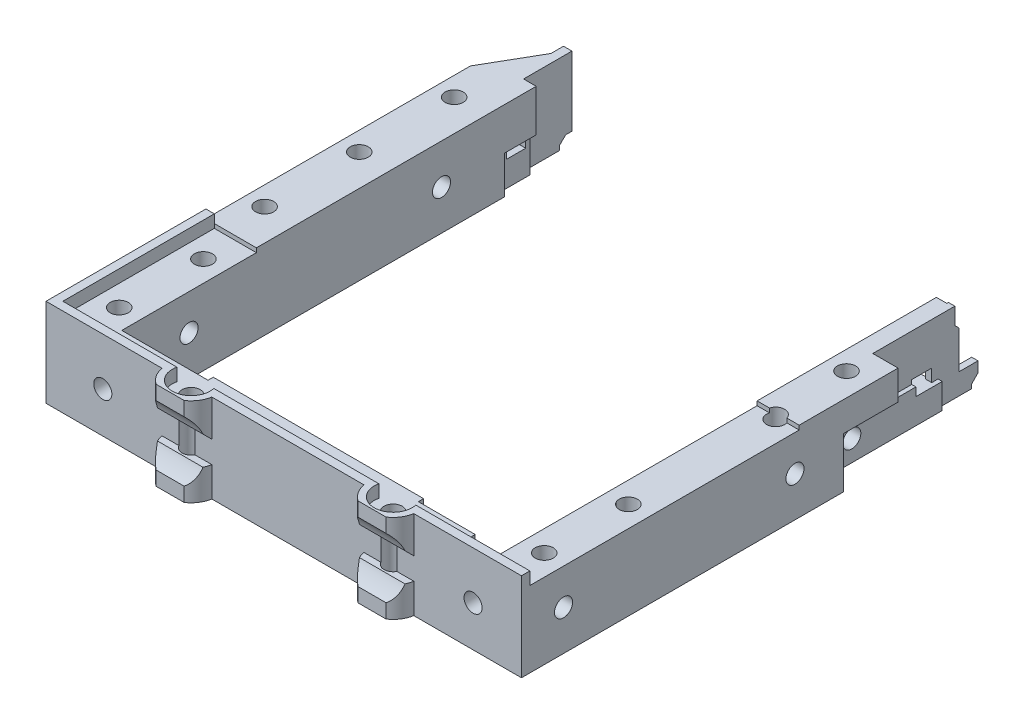
SolidWorks part; units mm, degrees
ref_plane "前视基准面" through (0, 0, 0) normal (0, 0, 1) x (1, 0, 0)
ref_plane "上视基准面" through (0, 0, 0) normal (0, 1, 0) x (1, 0, 0)
ref_plane "右视基准面" through (0, 0, 0) normal (1, 0, 0) x (0, 0, -1)
sketch "草图2" plane through (0, 0, 0) normal (0, 1, 0) x (1, 0, 0)
  line L0 (0, 0) -> (0, -10) construction
  line L1 (-45.5, 0) -> (45.5, 0)
  line L2 (45.5, 0) -> (45.5, 93)
  line L3 (45.5, 93) -> (55.5, 93)
  line L4 (55.5, 93) -> (55.5, -10)
  line L5 (55.5, -10) -> (-55.5, -10)
  line L6 (-45.5, 93) -> (-55.5, 93)
  line L7 (-55.5, 93) -> (-55.5, -10)
  line L8 (-45.5, 0) -> (-45.5, 93)
  dimension "D1" = 10
  dimension "D2" = 10
  dimension "D3" = 45.5
  dimension "D4" = 93
extrude "凸台-拉伸1" add sketch "草图2" along normal blind 18
sketch "草图3" plane through (0, 18, 0) normal (0, 1, 0) x (1, 0, 0)
  line L0 (55.5, 93) -> (45.5, 93) construction
  line L1 (45.5, 93) -> (45.5, 0) construction
  circle A0 centre (50, 76.75) radius 2.15
  dimension "D1" = 16.25
  dimension "D2" = 4.3
  dimension "D3" = 4.5
extrude "切除-拉伸1" cut sketch "草图3" against normal through all
sketch "草图4" plane through (55.5, 0, 0) normal (1, 0, 0) x (0, 0, -1)
  line L0 (-10, 0) -> (93, 0) construction
  line L1 (93, 18) -> (85.5, 18)
  line L2 (93, 18) -> (93, 0)
  line L3 (93, 0) -> (85.5, 0)
  line L4 (85.5, 18) -> (85.5, 0)
  line L5 (93, 18) -> (85.5, 0) construction
  line L6 (93, 0) -> (85.5, 18) construction
  point P4 (89.25, 9)
  dimension "D1" = 7.5
extrude "切除-拉伸2" cut sketch "草图4" against normal blind 6
sketch "草图5" plane through (55.5, 0, 0) normal (1, 0, 0) x (0, 0, -1)
  line L0 (85.5, 18) -> (85.5, 0) construction
  line L1 (85.5, 12) -> (70.5, 12)
  line L2 (85.5, 12) -> (85.5, 0)
  line L3 (85.5, 0) -> (70.5, 0)
  line L4 (70.5, 12) -> (70.5, 0)
  line L5 (85.5, 12) -> (70.5, 0) construction
  line L6 (85.5, 0) -> (70.5, 12) construction
  line L7 (-10, 0) -> (85.5, 0) construction
  line L8 (-10, 18) -> (85.5, 18) construction
  point P4 (78, 6)
  dimension "D1" = 6
  dimension "D2" = 15
extrude "切除-拉伸3" cut sketch "草图5" against normal up to surface (6 mm away) up to face at (49.5, 9, -89.25)
sketch "草图6" plane through (49.5, 0, 0) normal (1, 0, 0) x (0, 0, -1)
  line L1 (93, 0) -> (91, 0)
  line L2 (93, 0) -> (93, 9)
  line L3 (93, 9) -> (91, 9)
  line L4 (91, 0) -> (91, 9)
  line L5 (93, 0) -> (91, 9) construction
  line L6 (93, 9) -> (91, 0) construction
  point P4 (92, 4.5)
  dimension "D1" = 9
  dimension "D2" = 2
extrude "切除-拉伸4" cut sketch "草图6" against normal up to next
sketch "草图7" plane through (0, 18, 0) normal (0, 1, 0) x (1, 0, 0)
  line L0 (-45.5, 0) -> (-45.5, 93) construction
  line L1 (-55.5, 93) -> (-45.5, 93)
  line L2 (-55.5, 93) -> (-55.5, 32)
  line L3 (-55.5, 32) -> (-45.5, 32)
  line L4 (-45.5, 93) -> (-45.5, 32)
  line L5 (-55.5, 93) -> (-45.5, 32) construction
  line L6 (-55.5, 32) -> (-45.5, 93) construction
  point P4 (-50.5, 62.5)
  dimension "D1" = 61
extrude "凸台-拉伸2" add sketch "草图7" along normal blind 1
sketch "草图8" plane through (-55.5, 0, 0) normal (-1, 0, 0) x (0, 0, 1)
  line L1 (-32, 19) -> (-93, 19)
  line L2 (-32, 19) -> (-32, 0)
  line L3 (-32, 0) -> (-93, 0)
  line L4 (-93, 19) -> (-93, 0)
  line L5 (-32, 19) -> (-93, 0) construction
  line L6 (-32, 0) -> (-93, 19) construction
  point P4 (-62.5, 9.5)
extrude "凸台-拉伸3" add sketch "草图8" along normal blind 4
sketch "草图9" plane through (-55.5, 0, 0) normal (-1, 0, 0) x (0, 0, 1)
  line L1 (10, 0) -> (-32, 0)
  line L2 (10, 0) -> (10, 19)
  line L3 (10, 19) -> (-32, 19)
  line L4 (-32, 0) -> (-32, 19)
  line L5 (10, 0) -> (-32, 19) construction
  line L6 (10, 19) -> (-32, 0) construction
  point P4 (-11, 9.5)
extrude "凸台-拉伸4" add sketch "草图9" along normal blind 2
sketch "草图10" plane through (0, 18, 0) normal (0, 1, 0) x (1, 0, 0)
  line L0 (-57.5, -10) -> (-57.5, 32) construction
  line L1 (-55.5, -10) -> (55.5, -10) construction
  circle A0 centre (-50.5, 4.4) radius 2.15
  circle A1 centre (-50.5, 24.4) radius 2.15
  circle A2 centre (-24, -5) radius 2.15
  circle A3 centre (24, -5) radius 2.15
  dimension "D1" = 4.3
  dimension "D2" = 7
  dimension "D3" = 14.4
  dimension "D4" = 20
  dimension "D5" = 5
  dimension "D6" = 33.5
  dimension "D7" = 48
extrude "切除-拉伸5" cut sketch "草图10" against normal blind 6
sketch "草图11" plane through (0, 0, 0) normal (0, 0, -1) x (-1, 0, 0)
  line L0 (-45.5, 18) -> (45.5, 18) construction
  line L1 (-25, 18) -> (25, 18)
  line L2 (-25, 18) -> (-25, 0)
  line L3 (-25, 0) -> (25, 0)
  line L4 (25, 18) -> (25, 0)
  line L5 (-25, 18) -> (25, 0) construction
  line L6 (-25, 0) -> (25, 18) construction
  line L7 (-45.5, 0) -> (45.5, 0) construction
  point P4 (0, 9)
  dimension "D1" = 50
extrude "凸台-拉伸5" add sketch "草图11" along normal blind 1.25
sketch "草图12" plane through (0, 18, 0) normal (0, 1, 0) x (1, 0, 0)
  line L0 (49.5, 93) -> (45.5, 93)
  line L1 (45.5, 93) -> (45.5, 60)
  line L2 (45.5, 93) -> (45.5, 0) construction
  line L3 (45.5, 60) -> (55.5, 60)
  line L4 (55.5, -10) -> (55.5, 85.5) construction
  line L5 (55.5, 60) -> (55.5, 85.5)
  line L6 (55.5, 85.5) -> (49.5, 85.5)
  line L7 (49.5, 85.5) -> (49.5, 93)
  circle A0 centre (50, 76.75) radius 2.15 construction
  circle A1 centre (50, 76.75) radius 2.15
  dimension "D1" = 33
extrude "凸台-拉伸6" add sketch "草图12" along normal blind 1
sketch "草图13" plane through (0, 18, 0) normal (0, 1, 0) x (1, 0, 0)
  line L1 (45.5, 0) -> (38.5, 0)
  line L2 (45.5, 0) -> (45.5, -2)
  line L3 (45.5, -2) -> (38.5, -2)
  line L4 (38.5, 0) -> (38.5, -2)
  line L5 (45.5, 0) -> (38.5, -2) construction
  line L6 (45.5, -2) -> (38.5, 0) construction
  point P4 (42, -1)
  dimension "D1" = 7
  dimension "D2" = 2
extrude "切除-拉伸6" cut sketch "草图13" against normal up to surface (18 mm away) up to face at (4.075, 0, -39.3889)
sketch "草图14" plane through (0, 18, 0) normal (0, 1, 0) x (1, 0, 0)
  line L0 (55.5, -10) -> (55.5, 60) construction
  line L1 (-57.5, -10) -> (-27.3166, -10)
  line L2 (-57.5, -10) -> (-57.5, -6)
  line L3 (-57.5, -6) -> (-29.9161, -6)
  line L4 (55.5, -10) -> (55.5, -6)
  line L5 (-18.0839, -6) -> (18.0839, -6)
  line L6 (-20.6834, -10) -> (20.6834, -10)
  line L7 (29.9161, -6) -> (55.5, -6)
  line L8 (27.3166, -10) -> (55.5, -10)
  arc A0 (-29.9161, -6) -> (-27.3166, -10) centre (-24, -5) ccw
  arc A1 (18.0839, -6) -> (20.6834, -10) centre (24, -5) ccw
  arc A2 (-20.6834, -10) -> (-18.0839, -6) centre (-24, -5) ccw
  arc A3 (27.3166, -10) -> (29.9161, -6) centre (24, -5) ccw
  dimension "D2" = 12
  dimension "D3" = 12
  dimension "D1" = 4
extrude "切除-拉伸7" cut sketch "草图14" against normal through all and the other way through all
sketch "草图16" plane through (0, 18, 0) normal (0, 1, 0) x (1, 0, 0)
  line L0 (55.5, -6) -> (55.5, 60) construction
  line L1 (-55.5, -6) -> (-29.9161, -6)
  line L2 (-55.5, -6) -> (-55.5, -4)
  line L3 (-55.5, -4) -> (-29.9161, -4)
  line L4 (55.5, -6) -> (55.5, -4)
  line L5 (-18.0839, -4) -> (18.0839, -4)
  line L6 (-18.0839, -6) -> (18.0839, -6)
  line L7 (29.9161, -4) -> (55.5, -4)
  line L8 (29.9161, -6) -> (55.5, -6)
  arc A0 (-29.9161, -4) -> (-29.9161, -6) centre (-24, -5) ccw
  arc A1 (18.0839, -4) -> (18.0839, -6) centre (24, -5) ccw
  arc A2 (-18.0839, -6) -> (-18.0839, -4) centre (-24, -5) ccw
  arc A3 (29.9161, -6) -> (29.9161, -4) centre (24, -5) ccw
  dimension "D1" = 2
extrude "凸台-拉伸7" add sketch "草图16" along normal up to surface (1 mm away) up to face at (-54.5, 19, -37.75)
sketch "草图18" plane through (0, 19, 0) normal (0, 1, 0) x (1, 0, 0)
  line L0 (-53, 86.45) -> (-53, 41.45) construction
  line L1 (-59.5, 32) -> (-59.5, 93) construction
  line L2 (-45.5, 93) -> (-59.5, 93) construction
  circle A0 centre (-53, 86.45) radius 2.15
  circle A1 centre (-53, 63.95) radius 2.15
  circle A2 centre (-53, 41.45) radius 2.15
  dimension "D1" = 4.3
  dimension "D2" = 6.5
  dimension "D3" = 6.55
  dimension "D4" = 45
extrude "切除-拉伸8" cut sketch "草图18" against normal blind 6
sketch "草图19" plane through (0, 12, 0) normal (0, 1, 0) x (1, 0, 0)
  circle A0 centre (24, -5) radius 2.15 construction
  circle A1 centre (-24, -5) radius 2.15 construction
  circle A2 centre (24, -5) radius 2.15
  circle A3 centre (-24, -5) radius 2.15
extrude "切除-拉伸9" cut sketch "草图19" against normal through all
sketch "草图20" plane through (0, 13, 0) normal (0, 1, 0) x (1, 0, 0)
  line L0 (0, 0) -> (0, 86.45) construction
  circle A0 centre (-50.5, 4.4) radius 2.15 construction
  circle A1 centre (-50.5, 24.4) radius 2.15 construction
  circle A2 centre (-53, 41.45) radius 2.15 construction
  circle A3 centre (-53, 63.95) radius 2.15 construction
  circle A4 centre (-53, 86.45) radius 2.15 construction
  circle A5 centre (-50.5, 4.4) radius 2.15
  circle A6 centre (-50.5, 24.4) radius 2.15
  circle A7 centre (-53, 41.45) radius 2.15
  circle A8 centre (-53, 63.95) radius 2.15
  circle A9 centre (-53, 86.45) radius 2.15
  circle A10 centre (50.5, 24.4) radius 2.15
  circle A11 centre (50.5, 4.4) radius 2.15
extrude "切除-拉伸10" cut sketch "草图20" against normal through all and the other way through all
sketch "草图21" plane through (0, 0, 0) normal (0, -1, 0) x (1, 0, 0)
  line L1 (-45.5, -93) -> (45.5, -93)
  line L2 (-45.5, -93) -> (-45.5, 2)
  line L3 (-45.5, 2) -> (45.5, 2)
  line L4 (45.5, -93) -> (45.5, 2)
extrude "凸台-拉伸8" [suppressed] add sketch "草图21" against normal blind 2
sketch "草图22" [suppressed] plane through (0, 2, 0) normal (0, 1, 0) x (1, 0, 0)
  line L1 (38.5, 0) -> (45.5, 0)
  line L2 (38.5, 0) -> (38.5, -2)
  line L3 (38.5, -2) -> (45.5, -2)
  line L4 (45.5, 0) -> (45.5, -2)
extrude "凸台-拉伸9" [suppressed] add sketch "草图22" along normal blind 15
sketch "草图23" plane through (0, 0, -32) normal (0, 0, 1) x (1, 0, 0)
  line L4 (-59.5, 0) -> (-57.5, 0)
  line L5 (-57.5, 0) -> (-57.5, 19)
  line L6 (-57.5, 19) -> (-59.5, 19)
  line L7 (-59.5, 19) -> (-59.5, 0)
  line L8 (-59.5, 0) -> (-57.5, 0)
  line L9 (-57.5, 0) -> (-57.5, 19)
  line L10 (-57.5, 19) -> (-59.5, 19)
  line L11 (-59.5, 19) -> (-59.5, 0)
  dimension "D1" = 0
extrude "切除-拉伸11" cut sketch "草图23" against normal through all
sketch "草图24" plane through (0, 19, 0) normal (0, 1, 0) x (1, 0, 0)
  line L0 (-45.5, 93) -> (-49.5, 93)
  line L1 (-45.5, 93) -> (-57.5, 93) construction
  line L2 (-49.5, 93) -> (-45.5, 89)
  line L3 (-45.5, 32) -> (-45.5, 93) construction
  line L4 (-45.5, 89) -> (-45.5, 93)
  dimension "D1" = 4
  dimension "D2" = 4
sketch "草图26" plane through (49.5, 0, 0) normal (1, 0, 0) x (0, 0, -1)
  line L0 (91, 0) -> (91, 6)
  line L2 (91, 9) -> (91, 0) construction
  line L3 (91, 6) -> (98, 6)
  line L4 (98, 6) -> (98, 9)
  line L5 (98, 9) -> (93, 9)
  line L6 (93, 9) -> (93, 19)
  line L7 (93, 19) -> (107, 19)
  line L8 (107, 19) -> (107, 0)
  line L9 (107, 0) -> (91, 0)
  dimension "D1" = 6
  dimension "D2" = 5
  dimension "D3" = 16
extrude "凸台-拉伸10" add sketch "草图26" against normal offset from surface (3 mm away) 1 contours L8 L9 L0 L3 L4 L5 L6 L7 up to face at (45.5, 11.5, -60.5)
sketch "草图27" plane through (46.5, 0, 0) normal (-1, 0, 0) x (0, 0, 1)
  line L0 (-98, 13) -> (-98, 0)
  line L1 (-91, 0) -> (-107, 0) construction
  line L2 (-98, 0) -> (-107, 0)
  line L3 (-107, 0) -> (-107, 19)
  line L4 (-98, 9) -> (-98, 6) construction
  line L5 (-93, 9) -> (-98, 9) construction
  line L6 (-98, 13) -> (-101.4641, 19)
  line L7 (-107, 19) -> (-93, 19) construction
  line L8 (-107, 19) -> (-101.4641, 19)
  dimension "D1" = 4
  dimension "D2" = 150
extrude "切除-拉伸13" cut sketch "草图27" against normal offset from surface (1.5 mm away) 2.5 up to face at (45.5, 11.5, -60.5)
sketch "草图28" plane through (46.5, 0, 0) normal (-1, 0, 0) x (0, 0, 1)
  line L5 (-101.4641, 19) -> (-98, 13)
  line L6 (-98, 13) -> (-98, 9)
  line L7 (-98, 9) -> (-93, 9)
  line L8 (-93, 9) -> (-93, 19)
  line L9 (-93, 19) -> (-101.4641, 19)
  line L10 (-101.4641, 19) -> (-98, 13)
  line L11 (-98, 13) -> (-98, 9)
  line L12 (-98, 9) -> (-93, 9)
  line L13 (-93, 9) -> (-93, 19)
  line L14 (-93, 19) -> (-101.4641, 19)
  dimension "D1" = 0
extrude "凸台-拉伸11" add sketch "草图28" along normal up to surface (1 mm away) up to face at (45.5, 11.5, -60.5)
sketch "草图29" plane through (49.5, 0, 0) normal (1, 0, 0) x (0, 0, -1)
  line L0 (85.5, 12) -> (85.5, 6)
  line L1 (85.5, 6) -> (99, 6)
  line L3 (99, 6) -> (99, 0)
  line L4 (99, 0) -> (78.8411, 0)
  line L5 (70.5, 0) -> (70.5, 12)
  line L6 (70.5, 12) -> (74.6589, 12)
  line L7 (98, 6) -> (98, 9) construction
  line L8 (91, 6) -> (98, 6) construction
  line L9 (78.8411, 12) -> (78.8411, 0)
  line L10 (78.8411, 0) -> (78.8411, 12) construction
  line L11 (74.6589, 0) -> (74.6589, 12)
  line L12 (78.8411, 12) -> (85.5, 12)
  line L13 (74.6589, 0) -> (70.5, 0)
  dimension "D1" = 1
extrude "凸台-拉伸12" add sketch "草图29" along normal offset from surface (1 mm away) 5 up to face at (45.5, 11.6667, -66.1627)
fillet "圆角1" radius 1 1 edges at (50, 6, -85.5)
sketch "草图30" plane through (49.5, 0, 0) normal (1, 0, 0) x (0, 0, -1)
  line L2 (107, 19) -> (107, 0) construction
  line L3 (107, 11) -> (107, 19)
  line L4 (107, 19) -> (101.5, 19)
  line L6 (107, 11) -> (102.5, 11)
  line L7 (101.5, 12) -> (101.5, 19)
  line L8 (85.5, 19) -> (85.5, 12) construction
  arc A0 (102.5, 11) -> (101.5, 12) centre (102.5, 12) cw
  dimension "D2" = 1
  dimension "D1" = 8
  dimension "D3" = 16
extrude "切除-拉伸14" cut sketch "草图30" against normal up to next
sketch "草图31" plane through (49.5, 0, 0) normal (1, 0, 0) x (0, 0, -1)
  line L0 (107, 1) -> (108.5, 2.5)
  line L1 (107, 11) -> (107, 0) construction
  line L2 (108.5, 2.5) -> (108.5, 11)
  line L3 (108.5, 11) -> (107, 11)
  line L6 (99, 0) -> (107, 0) construction
  line L8 (107, 11) -> (107, 1)
  dimension "D1" = 1.5
  dimension "D2" = 1
  dimension "D3" = 45
extrude "凸台-拉伸13" add sketch "草图31" against normal up to surface (1.5 mm away) up to face at (48, 9.9793, -101.2757)
sketch "草图32" plane through (49.5, 0, 0) normal (1, 0, 0) x (0, 0, -1)
  line L0 (99, 6) -> (86.5, 6) construction
  line L1 (91, 9) -> (92.75, 9)
  line L2 (91, 9) -> (91, 6)
  line L3 (91, 6) -> (92.75, 6)
  line L4 (92.75, 9) -> (92.75, 6)
  dimension "D1" = 1.75
extrude "凸台-拉伸14" add sketch "草图32" against normal up to surface (4 mm away) up to face at (45.5, 11.6667, -66.1627)
chamfer "倒角1" distance 1 angle 60 1 edges at (45.5, 6, -91.875) first distance on face at (46, 6, -91.875)
sketch "草图33" plane through (0, 19, 0) normal (0, 1, 0) x (1, 0, 0)
  circle A0 centre (-53, 86.45) radius 2.15
  circle A1 centre (-53, 86.45) radius 2.15 construction
extrude "凸台-拉伸16" add sketch "草图33" against normal up to surface (19 mm away) up to face at (19.4221, 0, -39.5712)
sketch "草图34" plane through (0, 19, 0) normal (0, 1, 0) x (1, 0, 0)
  line L1 (-45.5, 93) -> (-57.5, 93) construction
  line L2 (-53, 86.5) -> (-53, 63.95) construction
  circle A0 centre (-53, 86.5) radius 2.15
  circle A1 centre (-53, 63.95) radius 2.15 construction
  dimension "D2" = 6.5
extrude "切除-拉伸15" cut sketch "草图34" against normal up to next
sketch "草图35" plane through (0, 19, 0) normal (0, 1, 0) x (1, 0, 0)
  circle A0 centre (-53, 86.5) radius 5
  circle A1 centre (-53, 86.5) radius 2.15
  circle A2 centre (-53, 86.5) radius 2.15 construction
  dimension "D1" = 10
sketch "草图36" plane through (-57.5, 0, 0) normal (-1, 0, 0) x (0, 0, 1)
  line L0 (-93, 6) -> (-98.5, 6)
  line L1 (-93, 0) -> (-93, 19) construction
  line L2 (-98.5, 6) -> (-98.5, 9)
  line L3 (-98.5, 9) -> (-93, 9)
  line L4 (-91, 0) -> (-98, 0) construction
  line L5 (-92.75, 9) -> (-98, 9) construction
  line L6 (-93, 6) -> (-93, 0)
  line L7 (-93, 0) -> (-107, 0)
  line L8 (-107, 0) -> (-98, 0) construction
  line L9 (-93, 0) -> (6, 0) construction
  line L10 (-107, 0) -> (-107, 1)
  line L11 (-107, 1) -> (-108.5, 2.5)
  line L12 (-108.5, 2.5) -> (-110, 2.5)
  line L13 (-110, 2.5) -> (-110, 19)
  line L14 (-110, 19) -> (-93, 19)
  line L15 (-93, 19) -> (-93, 9)
  dimension "D1" = 5.5
  dimension "D2" = 6
  dimension "D3" = 14
  dimension "D4" = 1.5
extrude "凸台-拉伸18" add sketch "草图36" against normal up to surface (12 mm away) up to face at (-45.5, 12.3333, -41.6667)
sketch "草图38" plane through (0, 0, -92.75) normal (0, 0, -1) x (-1, 0, 0)
  line L0 (-46.5, 6) -> (-46.5, 8)
  line L1 (-46.5, 8) -> (-45.5, 9)
  line L2 (-45.5, 0) -> (-45.5, 18) construction
  line L3 (-45.5, 9) -> (-45.5, 6)
  line L4 (-45.5, 6) -> (-46.5, 6)
  dimension "D1" = 45
extrude "切除-拉伸16" cut sketch "草图38" against normal up to surface (1.75 mm away) up to face at (46, 3.433, -91)
sketch "草图39" plane through (-45.5, 0, 0) normal (1, 0, 0) x (0, 0, -1)
  line L0 (110, 2.5) -> (110, 19) construction
  line L1 (91, 9) -> (110, 9)
  line L2 (91, 9) -> (91, 0)
  line L3 (91, 0) -> (110, 0)
  line L4 (110, 9) -> (110, 0)
  line L5 (0, 0) -> (107, 0) construction
  line L6 (93, 9) -> (98.5, 9) construction
  line L7 (93, 9) -> (93, 6) construction
  dimension "D1" = 2
extrude "切除-拉伸17" cut sketch "草图39" against normal blind 1.5
chamfer "倒角2" distance 1.5 angle 45 1 edges at (-47, 9, -92)
sketch "草图40" plane through (-47, 0, 0) normal (1, 0, 0) x (0, 0, -1)
  line L0 (32, 19) -> (110, 19) construction
  line L1 (98.5, 19) -> (110, 19)
  line L2 (98.5, 19) -> (98.5, 0)
  line L3 (98.5, 0) -> (110, 0)
  line L4 (110, 19) -> (110, 0)
  line L5 (110, 9) -> (110, 19) construction
  line L7 (91, 0) -> (107, 0) construction
  line L8 (98.5, 6) -> (98.5, 9) construction
extrude "切除-拉伸18" cut sketch "草图40" against normal blind 1.5 and the other way blind 1.5
sketch "草图41" plane through (-57.5, 0, 0) normal (-1, 0, 0) x (0, 0, 1)
  line L0 (-107, 19) -> (-107, 0)
  line L1 (6, 19) -> (-110, 19) construction
  line L2 (-107, 0) -> (6, 0) construction
  line L3 (-93, 6) -> (-93, 7.5) construction
  line L4 (-107, 19) -> (-110, 19)
  line L5 (-110, 19) -> (-110, 2.5)
  line L6 (-110, 2.5) -> (-107, 0)
  dimension "D1" = 14
extrude "切除-拉伸19" cut sketch "草图41" against normal blind 7
chamfer "倒角3" distance 7 angle 60 1 edges at (-57.5, 9.5, -107) first distance on face at (-52.1667, 6.6667, -107)
sketch "草图42" plane through (0, 9, 0) normal (0, -1, 0) x (1, 0, 0)
  line L1 (-51.5, -93) -> (-51.5, -105.2679)
  line L2 (-57.5, -94.8756) -> (-50.5, -107) construction
  line L3 (-51.5, -105.2679) -> (-57.5, -94.8756)
  line L4 (-48.5, -98.5) -> (-48.5, -107) construction
  line L8 (-57.5, -94.8756) -> (-57.5, -93)
  line L9 (-57.5, -93) -> (-51.5, -93)
  line L10 (-45.5, -93) -> (-57.5, -93) construction
  dimension "D1" = 3
extrude "切除-拉伸20" cut sketch "草图42" along normal up to next
sketch "草图43" plane through (49.5, 0, 0) normal (1, 0, 0) x (0, 0, -1)
  line L0 (104, 23.9473) -> (104, -7.2516) construction
  line L1 (98, 6) -> (98, 9) construction
  line L2 (108.5, 2.5) -> (108.5, 11) construction
  line L3 (104, 11) -> (108.5, 11)
  line L4 (104, 11) -> (104, 4)
  line L5 (104, 4) -> (108.5, 4)
  line L6 (108.5, 11) -> (108.5, 4)
  line L7 (102.5, 11) -> (108.5, 11) construction
  line L8 (99, 6) -> (86.5, 6) construction
  dimension "D1" = 6
  dimension "D2" = 2
extrude "切除-拉伸21" cut sketch "草图43" against normal blind 0.7
fillet "圆角2" radius 2 1 edges at (49.15, 4, -104)
sketch "草图44" plane through (48.8, 0, 0) normal (1, 0, 0) x (0, 0, -1)
  line L0 (108.5, 5) -> (104, 5)
  line L1 (108.5, 4) -> (108.5, 11) construction
  line L2 (104, 11) -> (104, 6) construction
  line L3 (108.5, 11) -> (104, 11) construction
  line L4 (108.5, 5) -> (108.5, 11)
  line L5 (104, 11) -> (104, 6)
  line L6 (108.5, 11) -> (104, 11)
  line L7 (106, 4) -> (108.5, 4) construction
  line L8 (104, 6) -> (104, 5)
  dimension "D1" = 1
extrude "切除-拉伸22" cut sketch "草图44" against normal up to next and the other way up to next
sketch "草图45" plane through (48.8, 0, 0) normal (1, 0, 0) x (0, 0, -1)
  line L3 (108.5, 5) -> (104.2679, 5)
  line L4 (106, 4) -> (108.5, 4)
  line L5 (108.5, 4) -> (108.5, 5)
  line L6 (108.5, 5) -> (104.2679, 5)
  line L7 (106, 4) -> (108.5, 4)
  line L8 (108.5, 4) -> (108.5, 5)
  arc A1 (104.2679, 5) -> (106, 4) centre (106, 6) ccw
  arc A2 (104.2679, 5) -> (106, 4) centre (106, 6) ccw
  dimension "D1" = 0
extrude "凸台-拉伸19" add sketch "草图45" along normal up to surface (0.7 mm away) up to face at (49.5, 7.0927, -99.561)
sketch "草图46" plane through (49.5, 0, 0) normal (1, 0, 0) x (0, 0, -1)
  line L0 (99, 6) -> (86.5, 6) construction
  line L1 (98, 9) -> (97.5, 9)
  line L2 (98, 9) -> (98, 6)
  line L3 (98, 6) -> (97.5, 6)
  line L4 (97.5, 9) -> (97.5, 6)
  dimension "D1" = 0.5
extrude "凸台-拉伸20" add sketch "草图46" against normal up to surface (1.5 mm away) up to face at (48, 8.0923, -102.6969)
sketch "草图47" plane through (-51.5, 0, 0) normal (-1, 0, 0) x (0, 0, 1)
  line L1 (-98.5, 9) -> (-97.5, 9)
  line L2 (-98.5, 9) -> (-98.5, 6)
  line L3 (-98.5, 6) -> (-97.5, 6)
  line L4 (-97.5, 9) -> (-97.5, 6)
extrude "凸台-拉伸21" add sketch "草图47" against normal up to surface (4.5 mm away) up to face at (-47, 4.5, -94.1667)
sketch "草图48" plane through (49.5, 0, 0) normal (1, 0, 0) x (0, 0, -1)
  line L0 (85.5, 7) -> (85.5, 12) construction
  line L1 (85.5, 8) -> (83.5, 8)
  line L2 (85.5, 8) -> (85.5, 19)
  line L3 (85.5, 19) -> (83.5, 19)
  line L4 (83.5, 8) -> (83.5, 19)
  line L5 (60, 19) -> (85.5, 19) construction
  line L6 (92.75, 6) -> (86.5, 6) construction
  dimension "D1" = 2
  dimension "D2" = 2
extrude "切除-拉伸23" cut sketch "草图48" along normal up to next
fillet "圆角3" radius 0.5 2 edges at (50, 8, -85.5) (50, 8, -83.5)
sketch "草图49" plane through (48, 0, 0) normal (-1, 0, 0) x (0, 0, 1)
  line L0 (-98, 11) -> (-102.6188, 19)
  line L1 (-98, 9) -> (-98, 13) construction
  line L2 (-102.6188, 19) -> (-101.4641, 19)
  line L3 (-101.4641, 19) -> (-98, 13)
  line L4 (-98, 13) -> (-98, 11)
  dimension "D1" = 1
extrude "凸台-拉伸22" add sketch "草图49" along normal up to surface (2.5 mm away) up to face at (45.5, 11.4, -68.8214)
sketch "草图50" plane through (49.5, 0, 0) normal (1, 0, 0) x (0, 0, -1)
  line L1 (104, 11) -> (101.5, 11)
  line L2 (104, 11) -> (104, 19)
  line L3 (104, 19) -> (101.5, 19)
  line L4 (101.5, 11) -> (101.5, 19)
extrude "凸台-拉伸23" add sketch "草图50" against normal up to surface (1.5 mm away) up to face at (48, 7.0237, -102.0862)
sketch "草图51" plane through (48, 0, 0) normal (-1, 0, 0) x (0, 0, 1)
  line L1 (-104, 19) -> (-103, 19)
  line L2 (-104, 19) -> (-104, 14)
  line L3 (-104, 14) -> (-103, 14)
  line L4 (-103, 19) -> (-103, 14)
  dimension "D1" = 1
  dimension "D2" = 5
extrude "切除-拉伸24" cut sketch "草图51" against normal up to next
chamfer "倒角4" distance 1 angle 45 1 edges at (48.75, 14, -103)
sketch "草图52" plane through (0, 0, 0) normal (0, -1, 0) x (1, 0, 0)
  line L0 (50.5, -73.792) -> (50.5, -79.708)
  line L1 (50.5, -70.5) -> (50.5, -74.6589) construction
  line L2 (50.5, -83.5) -> (50.5, -78.8411) construction
  arc A0 (50.5, -73.792) -> (50.5, -79.708) centre (50, -76.75) ccw
  dimension "D1" = 6
extrude "凸台-拉伸25" add sketch "草图52" against normal up to surface (12 mm away) up to face at (52.4417, 12, -76.9167)
sketch "草图53" plane through (50.5, 0, 0) normal (1, 0, 0) x (0, 0, -1)
  line L0 (77.5, 12) -> (77.5, 0) construction
  line L1 (83.5, 12) -> (70.5, 12) construction
  line L2 (70.5, 0) -> (99, 0) construction
  line L3 (70.5, 12) -> (70.5, 0) construction
  circle A0 centre (77.5, 5) radius 2.15
  dimension "D1" = 4.3
  dimension "D3" = 5
  dimension "D2" = 7
extrude "切除-拉伸25" cut sketch "草图53" against normal up to next
sketch "草图54" plane through (0, 0, 0) normal (0, -1, 0) x (1, 0, 0)
  line L0 (50.5, -24.4) -> (50.5, -59.4) construction
  circle A0 centre (50.5, -59.4) radius 2.15
  dimension "D1" = 4.3
  dimension "D2" = 35
extrude "切除-拉伸26" cut sketch "草图54" against normal up to next
sketch "草图55" plane through (-57.5, 0, 0) normal (-1, 0, 0) x (0, 0, 1)
  line L0 (6, 9.5) -> (-76, 9.5) construction
  line L1 (6, 0) -> (6, 19) construction
  line L2 (-93, 0) -> (-93, 9) construction
  circle A0 centre (-76, 9.5) radius 2.15
  circle A1 centre (-16, 9.5) radius 2.15
  dimension "D2" = 60
  dimension "D3" = 4.3
  dimension "D1" = 17
extrude "切除-拉伸27" cut sketch "草图55" against normal up to surface (12 mm away) up to face at (-45.5, 11.2222, -59.5556)
sketch "草图56" plane through (55.5, 0, 0) normal (1, 0, 0) x (0, 0, -1)
  line L0 (-6, 9.5) -> (59, 9.5) construction
  line L1 (-6, 0) -> (-6, 19) construction
  circle A0 centre (4, 9.5) radius 2.15
  circle A1 centre (59, 9.5) radius 2.15
  dimension "D2" = 4.3
  dimension "D3" = 55
  dimension "D1" = 65
extrude "切除-拉伸28" cut sketch "草图56" against normal up to surface (10 mm away) up to face at (45.5, 5, -79.65)
sketch "草图57" plane through (55.5, 0, 0) normal (1, 0, 0) x (0, 0, -1)
  line L0 (-6, 10.5) -> (-17, 10.5) construction
  line L2 (-6, 0) -> (-6, 19) construction
  line L3 (-10, 0) -> (-6, 0) construction
  circle A0 centre (-17, 10.5) radius 10
  point P2 (-6, 10.9042)
  dimension "D1" = 20
  dimension "D2" = 11
  dimension "D3" = 10.5
extrude "切除-拉伸29" cut sketch "草图57" against normal up to surface (113 mm away) up to face at (-57.5, 9.5, -73.85)
sketch "草图58" plane through (55.5, 0, 0) normal (1, 0, 0) x (0, 0, -1)
  line L0 (-6, 0) -> (-6, 19) construction
  line L1 (-7.6, 13.9117) -> (-6, 13.9117)
  line L2 (-7.6, 13.9117) -> (-7.6, 7.0883)
  line L3 (-7.6, 7.0883) -> (-6, 7.0883)
  line L4 (-6, 13.9117) -> (-6, 7.0883)
  arc A0 (-10, 3.3586) -> (-10, 17.6414) centre (-17, 10.5) ccw construction
  dimension "D1" = 1.6
extrude "切除-拉伸30" cut sketch "草图58" against normal up to surface (113 mm away) up to face at (-57.5, 9.5, -73.85)
chamfer "倒角5" distance 1.6 angle 45 2 edges at (-27.9097, 13.9117, 6) (27.9097, 13.9117, 6)
sketch "草图59" plane through (0, 19, 0) normal (0, 1, 0) x (1, 0, 0)
  line L0 (-55.5, 32) -> (-57.5, 32)
  line L1 (55.5, -6) -> (55.5, -4) construction
  line L2 (55.5, -4) -> (29.9161, -4) construction
  line L3 (29.9161, -6) -> (55.5, -6) construction
  line L4 (-18.0839, -6) -> (18.0839, -6) construction
  line L5 (18.0839, -4) -> (-18.0839, -4) construction
  line L6 (55.5, -6) -> (55.5, -4)
  line L7 (55.5, -4) -> (29.9161, -4)
  line L8 (29.9161, -6) -> (55.5, -6)
  line L9 (-18.0839, -6) -> (18.0839, -6)
  line L10 (18.0839, -4) -> (-18.0839, -4)
  line L11 (-50.5, 110) -> (-50.5, 107)
  line L12 (-50.5, 107) -> (-57.5, 94.8756)
  line L13 (-57.5, 94.8756) -> (-57.5, -6)
  line L14 (-57.5, -6) -> (-29.9161, -6)
  line L15 (-29.9161, -4) -> (-55.5, -4)
  line L16 (-55.5, -4) -> (-55.5, 32)
  line L17 (-55.5, 32) -> (-45.5, 32)
  line L18 (-45.5, 32) -> (-45.5, 98.5)
  line L19 (-45.5, 98.5) -> (-48.5, 98.5)
  line L20 (-48.5, 98.5) -> (-48.5, 110)
  line L21 (-48.5, 110) -> (-50.5, 110)
  line L24 (-57.5, 32) -> (-57.5, -6)
  line L25 (-57.5, -6) -> (-29.9161, -6)
  line L26 (-29.9161, -4) -> (-55.5, -4)
  line L27 (-55.5, -4) -> (-55.5, 32)
  arc A0 (29.9161, -6) -> (29.9161, -4) centre (24, -5) ccw construction
  arc A1 (-29.9161, -4) -> (-29.9161, -6) centre (-24, -5) ccw
  arc A2 (-29.9161, -4) -> (-29.9161, -6) centre (-24, -5) ccw
  arc A3 (18.0839, -4) -> (18.0839, -6) centre (24, -5) ccw construction
  arc A4 (-18.0839, -6) -> (-18.0839, -4) centre (-24, -5) ccw construction
  arc A5 (29.9161, -6) -> (29.9161, -4) centre (24, -5) ccw
  arc A6 (18.0839, -4) -> (18.0839, -6) centre (24, -5) ccw
  arc A7 (-18.0839, -6) -> (-18.0839, -4) centre (-24, -5) ccw
  dimension "D1" = 0
extrude "凸台-拉伸26" add sketch "草图59" along normal blind 2
sketch "草图60" plane through (0, 18, 0) normal (0, 1, 0) x (1, 0, 0)
  line L0 (-29.9161, -4) -> (-28.3875, -4)
  line L1 (-27.3166, -10) -> (-20.6834, -10)
  line L2 (-19.6125, -4) -> (-18.0839, -4)
  line L3 (18.0839, -4) -> (19.6125, -4)
  line L4 (20.6834, -10) -> (27.3166, -10)
  line L5 (28.3875, -4) -> (29.9161, -4)
  arc A0 (-29.9161, -4) -> (-27.3166, -10) centre (-24, -5) ccw
  arc A1 (-28.3875, -4) -> (-19.6125, -4) centre (-24, -5) ccw
  arc A2 (-20.6834, -10) -> (-18.0839, -4) centre (-24, -5) ccw
  arc A3 (18.0839, -4) -> (20.6834, -10) centre (24, -5) ccw
  arc A4 (19.6125, -4) -> (28.3875, -4) centre (24, -5) ccw
  arc A5 (27.3166, -10) -> (29.9161, -4) centre (24, -5) ccw
  dimension "D1" = 1.5
  dimension "D2" = 1.5
extrude "凸台-拉伸27" add sketch "草图60" along normal up to surface (3 mm away) up to face at (-47.6527, 21, -7.3333)
sketch "草图61" plane through (0, 0, 6) normal (0, 0, 1) x (1, 0, 0)
  line L0 (-18.0839, 12.3117) -> (-18.0839, 7.0883) construction
  line L1 (-18.0839, 9.7) -> (-44, 9.7) construction
  line L2 (-18.0839, 9.7) -> (44, 9.7) construction
  line L3 (0, 21) -> (0, 0) construction
  line L4 (-18.0839, 21) -> (18.0839, 21) construction
  circle A0 centre (-44, 9.7) radius 2.15
  circle A1 centre (44, 9.7) radius 2.15
  dimension "D2" = 4.3
  dimension "D1" = 88
extrude "切除-拉伸31" cut sketch "草图61" against normal up to surface (6 mm away) up to face at (-35.25, 9, 0)
sketch "草图62" plane through (49.5, 0, 0) normal (1, 0, 0) x (0, 0, -1)
  line L0 (99, 6) -> (86.5, 6) construction
  line L1 (85, 8) -> (92.75, 8)
  line L2 (85, 8) -> (85, 6)
  line L3 (85, 6) -> (92.75, 6)
  line L4 (92.75, 8) -> (92.75, 6)
extrude "凸台-拉伸28" add sketch "草图62" along normal up to surface (1 mm away) up to face at (50.5, 5, -79.65)
equation "\"1、\"=4"
